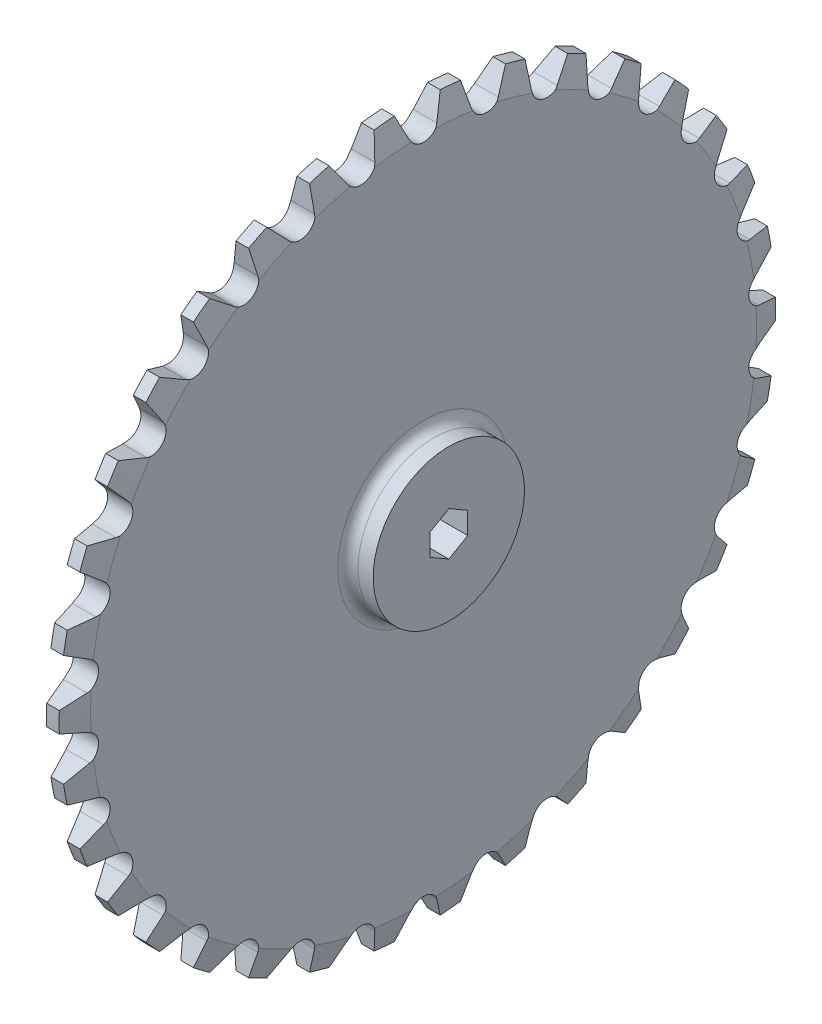
SolidWorks part; units mm, degrees
material "Nylon 101"
ref_plane "Front Plane" through (0, 0, 0) normal (0, 0, 1) x (1, 0, 0)
ref_plane "Top Plane" through (0, 0, 0) normal (0, 1, 0) x (1, 0, 0)
ref_plane "Right Plane" through (0, 0, 0) normal (1, 0, 0) x (0, 0, -1)
sketch "Sketch1" plane through (0, 0, 0) normal (0, 1, 0) x (1, 0, 0)
  line L0 (-6.35, 83.82) -> (-4.7625, 90.17)
  line L1 (0, 0) -> (-6.35, 0)
  line L2 (0, 0) -> (0, 83.82)
  line L3 (0, 83.82) -> (-6.35, 83.82)
  line L4 (-6.35, 0) -> (-6.35, 83.82)
  line L5 (-4.7625, 90.17) -> (-1.5875, 90.17)
  line L6 (-1.5875, 90.17) -> (0, 83.82)
  line L8 (0, 0) -> (6.35, 0)
  line L9 (0, 0) -> (0, 19.05)
  line L10 (0, 19.05) -> (6.35, 19.05)
  line L11 (6.35, 0) -> (6.35, 19.05)
  line L12 (-6.35, 0) -> (-15.875, 0)
  line L13 (-6.35, 0) -> (-6.35, 19.05)
  line L14 (-6.35, 19.05) -> (-15.875, 19.05)
  line L15 (-15.875, 0) -> (-15.875, 19.05)
  point P7 (-3.175, 90.17)
  point P8 (-3.175, 83.82)
  dimension "D1" = 83.82
  dimension "D2" = 6.35
  dimension "D3" = 19.05
  dimension "D4" = 9.525
  dimension "D5" = 3.175
  dimension "D6" = 6.35
  dimension "D7" = 6.35
revolve "Revolve1" add sketch "Sketch1" angle 360 about L1 region at (-3.175, 0, -86.6422) region at (-3.175, 0, -41.91) region at (-11.1125, 0, -9.525) region at (3.175, 0, -9.525)
sketch "Sketch2" plane through (0, 0, 0) normal (1, 0, 0) x (0, 0, -1)
  line L0 (0, 0) -> (0, 90.17) construction
  line L1 (-3.52, 84.5682) -> (-8.3801, 96.3015)
  line L2 (3.52, 84.5682) -> (8.3801, 96.3015)
  line L3 (-8.3801, 96.3015) -> (8.3801, 96.3015)
  line L6 (0, 86.0262) -> (-15.8073, 84.5615)
  line L7 (-15.8073, 84.5615) -> (-31.0763, 80.2171)
  line L8 (-31.0763, 80.2171) -> (-45.287, 73.141)
  line L9 (-45.287, 73.141) -> (-57.9555, 63.5742)
  line L10 (-57.9555, 63.5742) -> (-68.6504, 51.8424)
  line L11 (-68.6504, 51.8424) -> (-77.0075, 38.3452)
  line L12 (-77.0075, 38.3452) -> (-82.7422, 23.5422)
  line L13 (-82.7422, 23.5422) -> (-85.6593, 7.9375)
  line L14 (-85.6593, 7.9375) -> (-85.6593, -7.9375)
  line L15 (-85.6593, -7.9375) -> (-82.7422, -23.5422)
  line L16 (-82.7422, -23.5422) -> (-77.0075, -38.3452)
  line L17 (-77.0075, -38.3452) -> (-68.6504, -51.8424)
  line L18 (-68.6504, -51.8424) -> (-57.9555, -63.5742)
  line L19 (-57.9555, -63.5742) -> (-45.287, -73.141)
  line L20 (-45.287, -73.141) -> (-31.0763, -80.2171)
  line L21 (-31.0763, -80.2171) -> (-15.8073, -84.5615)
  line L22 (-15.8073, -84.5615) -> (0, -86.0262)
  line L23 (0, -86.0262) -> (15.8073, -84.5615)
  line L24 (15.8073, -84.5615) -> (31.0763, -80.2171)
  line L25 (31.0763, -80.2171) -> (45.287, -73.141)
  line L26 (45.287, -73.141) -> (57.9555, -63.5742)
  line L27 (57.9555, -63.5742) -> (68.6504, -51.8424)
  line L28 (68.6504, -51.8424) -> (77.0075, -38.3452)
  line L29 (77.0075, -38.3452) -> (82.7422, -23.5422)
  line L30 (82.7422, -23.5422) -> (85.6593, -7.9375)
  line L31 (85.6593, -7.9375) -> (85.6593, 7.9375)
  line L32 (85.6593, 7.9375) -> (82.7422, 23.5422)
  line L33 (82.7422, 23.5422) -> (77.0075, 38.3452)
  line L34 (77.0075, 38.3452) -> (68.6504, 51.8424)
  line L35 (68.6504, 51.8424) -> (57.9555, 63.5742)
  line L36 (57.9555, 63.5742) -> (45.287, 73.141)
  line L37 (45.287, 73.141) -> (31.0763, 80.2171)
  line L38 (31.0763, 80.2171) -> (15.8073, 84.5615)
  line L39 (15.8073, 84.5615) -> (0, 86.0262)
  circle A0 centre (0, 0) radius 90.17 construction
  circle A2 centre (0, 0) radius 90.17 construction
  circle A3 centre (0, 86.0262) radius 3.81
  circle A4 centre (0, 0) radius 85.6593 construction
  dimension "D2" = 7.62
  dimension "D3" = 22.5
  dimension "D4" = 12.7
  dimension "D6" = 15.875
extrude "Cut-Extrude2" cut sketch "Sketch2" against normal through all both contours A3 L6 | L6 A3 | A3 L2 L3 L1 L6 | A3 L2 | A3 L6 L1 region at (0, 84.3155, 0) region at (0, 85.3882, 3.8041) region at (0, 92.6209, 0) region at (0, 85.3882, -3.8041) region at (0, 87.5469, 0)
pattern_circular "CirPattern1" count 34 over 360 about axis through (6.35, 0, 0) along (1, 0, 0) of "Cut-Extrude2"
sketch "Sketch3" plane through (-15.875, 0, 0) normal (-1, 0, 0) x (0, 0, 1)
  line L1 (0, 5.4993) -> (-4.7625, 2.7496)
  line L2 (-4.7625, 2.7496) -> (-4.7625, -2.7496)
  line L3 (-4.7625, -2.7496) -> (0, -5.4993)
  line L4 (0, -5.4993) -> (4.7625, -2.7496)
  line L5 (4.7625, -2.7496) -> (4.7625, 2.7496)
  line L6 (4.7625, 2.7496) -> (0, 5.4993)
  circle A0 centre (0, 0) radius 4.7625 construction
  dimension "D1" = 9.525
extrude "Cut-Extrude3" cut sketch "Sketch3" against normal through all both
fillet "Fillet1" radius 2.54 2 edges at (0, 0, -19.05) (-6.35, 0, -19.05)
